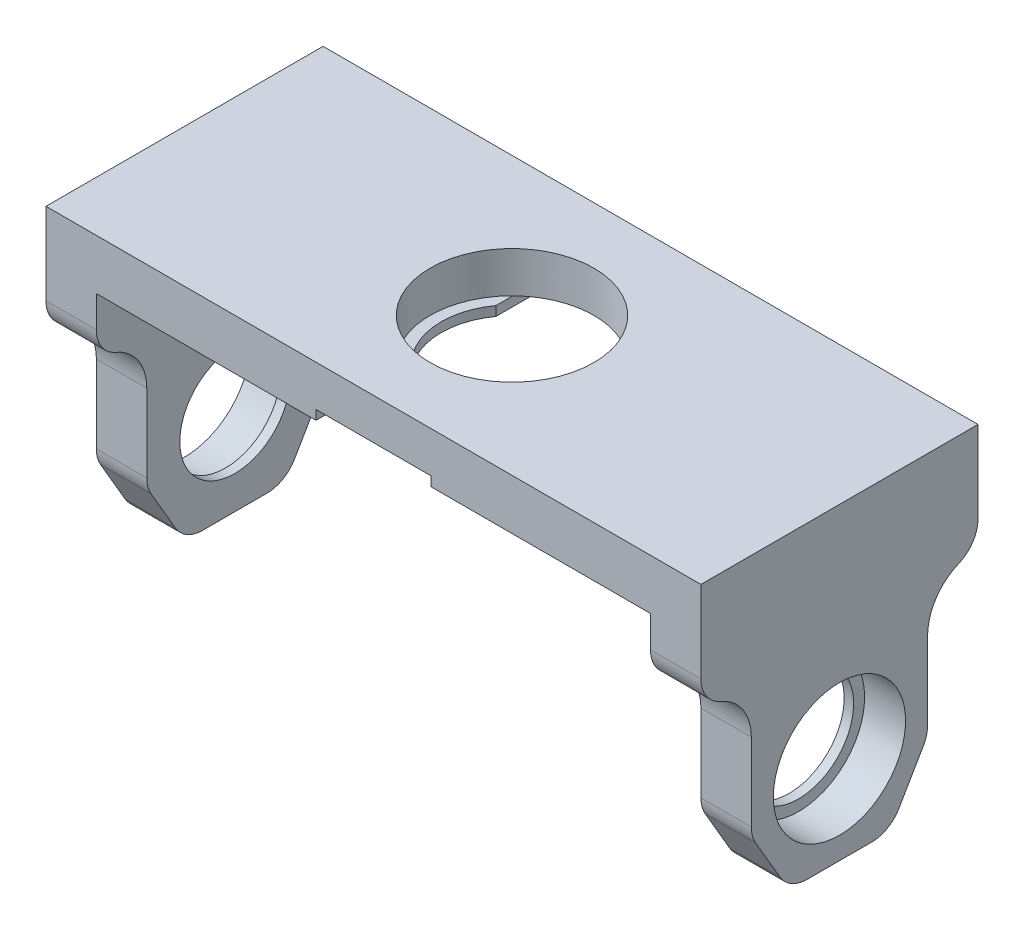
SolidWorks part; units mm, degrees
ref_plane "Front Plane" through (0, 0, 0) normal (0, 0, 1) x (1, 0, 0)
ref_plane "Top Plane" through (0, 0, 0) normal (0, 1, 0) x (1, 0, 0)
ref_plane "Right Plane" through (0, 0, 0) normal (1, 0, 0) x (0, 0, -1)
sketch "Sketch1" plane through (0, 0, 0) normal (0, 0, 1) x (1, 0, 0)
  line L0 (44, 0) -> (-44, 0)
  line L1 (-44, 0) -> (-44, -41)
  line L2 (-44, -41) -> (-52, -41)
  line L3 (-52, -41) -> (-52, 8)
  line L4 (-52, 8) -> (52, 8)
  line L5 (52, 8) -> (52, -41)
  line L6 (52, -41) -> (44, -41)
  line L7 (44, -41) -> (44, 0)
  point P4 (0, 0)
  dimension "D1" = 88
  dimension "D2" = 8
  dimension "D3" = 8
  dimension "D4" = 49
extrude "Boss-Extrude1" add sketch "Sketch1" along normal blind 44
sketch "Sketch4" plane through (-52, 0, 0) normal (-1, 0, 0) x (0, 0, 1)
  line L0 (0, -27) -> (22, -27) construction
  line L1 (0, 8) -> (0, -41) construction
  line L2 (22, -27) -> (44, -27) construction
  line L3 (44, 8) -> (44, -41) construction
  line L5 (44, -41) -> (0, -41) construction
  point P0 (22, -27)
  dimension "D1" = 14
hole_wizard "Ø21.0 (21) Diameter Hole1" positions "Sketch4" profile "Sketch3" hole size "Ø21.0" standard "DIN" end condition through all
sketch "Sketch3" plane through (-52, -27, 22) normal (0, 1, 0) x (0, 0, 1)
  line L0 (0, 0) -> (0, 104)
  line L1 (0, 104) -> (10.5, 104)
  line L2 (10.5, 104) -> (10.5, 0)
  line L5 (10.5, 0) -> (0, 0)
  line L11 (0, -6.35) -> (0, 107.95) construction
  dimension "Thru Hole Dia." = 21
  dimension "Thru Hole Depth" = 104
sketch "Sketch8" plane through (0, 8, 0) normal (0, 1, 0) x (1, 0, 0)
  line L0 (-52, -22) -> (0, -22) construction
  line L1 (-52, -44) -> (-52, 0) construction
  line L2 (0, -22) -> (52, -22) construction
  line L3 (52, -44) -> (52, 0) construction
  line L5 (0, 0) -> (0, -22) construction
  line L6 (0, -22) -> (0, -44) construction
  line L7 (52, -44) -> (-52, -44) construction
  point P2 (0, -22)
  point P23 (0, -22)
hole_wizard "Ø26.0 (26) Diameter Hole1" positions "Sketch8" profile "Sketch6" hole size "Ø26.0" standard "DIN" end condition through all
sketch "Sketch6" plane through (0, 8, 22) normal (1, 0, 0) x (0, 0, 1)
  line L0 (0, 0) -> (0, 49)
  line L1 (0, 49) -> (13, 49)
  line L2 (13, 49) -> (13, 0)
  line L5 (13, 0) -> (0, 0)
  line L11 (0, -6.35) -> (0, 107.95) construction
  dimension "Thru Hole Dia." = 26
  dimension "Thru Hole Depth" = 49
sketch "Sketch9" plane through (44, 0, 0) normal (-1, 0, 0) x (0, 0, 1)
  circle A0 centre (22, -27) radius 10.5 construction
  circle A1 centre (22, -27) radius 10.5
  circle A2 centre (22, -27) radius 8.75
  dimension "D1" = 1.75
extrude "Boss-Extrude2" add sketch "Sketch9" against normal blind 1.5
extrude "Boss-Extrude3" add sketch "Sketch9<2>" along normal blind 1.5 from surface starting at face at (-44, -37.5, 22)
sketch "Sketch9<2>" plane through (44, 0, 0) normal (-1, 0, 0) x (0, 0, 1) same geometry as "Sketch9"
sketch "Sketch16" plane through (0, 0, 0) normal (0, 1, 0) x (1, 0, 0)
  circle A0 centre (0, -22) radius 13 construction
  circle A1 centre (0, -22) radius 13
  circle A2 centre (0, -22) radius 11.25
  dimension "D1" = 1.75
extrude "Boss-Extrude4" add sketch "Sketch16" along normal blind 1.5
sketch "Sketch17" plane through (0, 0, 44) normal (0, 0, 1) x (1, 0, 0)
  line L0 (-44, 0) -> (44, 0) construction
  line L1 (-9.125, 0) -> (9.125, 0)
  line L2 (-9.125, 0) -> (-9.125, 1.5)
  line L3 (-9.125, 1.5) -> (9.125, 1.5)
  line L4 (9.125, 0) -> (9.125, 1.5)
  line L5 (0, 1.5) -> (0, 0) construction
  dimension "D1" = 18.25
  dimension "D2" = 1.5
extrude "Cut-Extrude1" cut sketch "Sketch17" against normal through all
sketch "Sketch19" plane through (-52, 0, 0) normal (-1, 0, 0) x (0, 0, 1)
  line L0 (0, 8) -> (0, -41) construction
  line L1 (44, 8) -> (0, 8) construction
  line L2 (0, -17) -> (14, -41)
  line L3 (44, -41) -> (0, -41) construction
  line L4 (14, -41) -> (0, -41)
  line L5 (0, -41) -> (0, -17)
  line L6 (8, -17) -> (8, -30.7143)
  line L7 (22, -27) -> (22, -10.1382) construction
  line L8 (36, -17) -> (36, -30.7143)
  line L9 (30, -41) -> (44, -41)
  line L10 (44, -17) -> (30, -41)
  line L11 (44, -41) -> (44, -17)
  circle A0 centre (0, -17) radius 8
  circle A1 centre (44, -17) radius 8
  line M3 (0, 8) -> (0, -41)
  line M6 (44, -41) -> (44, 8)
  line M8 (0, -41) -> (44, -41)
  dimension "D1" = 16
  dimension "D2" = 25
  dimension "D3" = 14
extrude "Cut-Extrude3" cut sketch "Sketch19" against normal through all contours L2 A0 M3 | A0 L5 L2 M8 | A0 L2 L6 | L10 A1 L8 | A1 L10 M6 | A1 L10 M6 M8 | A1 | L9 L11 L10 | A0 region at (-52, -34.2202, 38.9653) region at (-52, -34.2202, 5.0347) region at (-52, -24.7293, 6.7544) region at (-52, -15.9718, 3.8034) region at (-52, -24.7293, 37.2456) region at (-52, -15.9718, 40.1966)
fillet "Fillet3" radius 5 12 edges at (48, -9, 0) (-48, -9, 0) (48, -30.7143, 8) (-48, -30.7143, 8) (-48, -9, 44) (48, -9, 44) (48, -30.7143, 36) (-48, -30.7143, 36) (-48, -41, 14) (48, -41, 14) (48, -41, 30) (-48, -41, 30)
